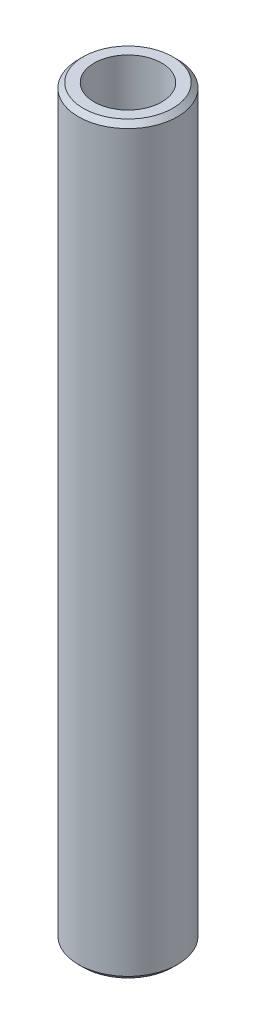
SolidWorks part; units mm, degrees
ref_plane "Front Plane" through (0, 0, 0) normal (0, 0, 1) x (1, 0, 0)
ref_plane "Top Plane" through (0, 0, 0) normal (0, 1, 0) x (1, 0, 0)
ref_plane "Right Plane" through (0, 0, 0) normal (1, 0, 0) x (0, 0, -1)
sketch "Sketch1" plane through (0, 0, 0) normal (0, 1, 0) x (1, 0, 0)
  circle A0 centre (0, 0) radius 40
  dimension "SHAFT_OD" = 80
extrude "Boss-Extrude1" add sketch "Sketch1" along normal blind 600
sketch "Sketch2" plane through (0, 0, 0) normal (0, 1, 0) x (1, 0, 0)
  circle A0 centre (0, 0) radius 27.2508
  dimension "BORE_D" = 54.5016
extrude "Cut-Extrude1" cut sketch "Sketch2" along normal through all
chamfer "Chamfer1" distance 3.92 angle 45 2 edges at (0, 600, 40) (0, 0, 40)
